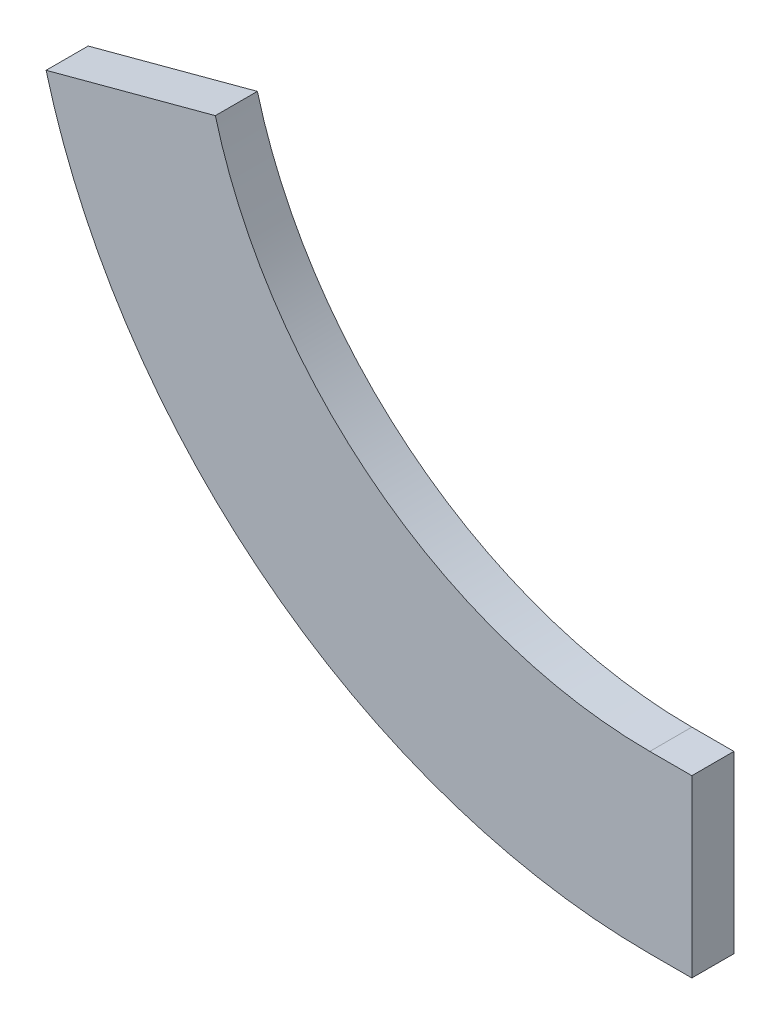
SolidWorks part; units mm, degrees
ref_plane "Front Plane" through (0, 0, 0) normal (0, 0, 1) x (1, 0, 0)
ref_plane "Top Plane" through (0, 0, 0) normal (0, 1, 0) x (1, 0, 0)
ref_plane "Right Plane" through (0, 0, 0) normal (1, 0, 0) x (0, 0, -1)
sketch "Sketch1" plane through (0, 0, 0) normal (0, 0, 1) x (1, 0, 0)
  line L0 (-79.4411, -31.75) -> (-82.4891, -31.75)
  line L1 (-113.979, -7.587) -> (-126.2462, -10.874)
  line L2 (-82.4891, -44.45) -> (-79.4411, -44.45)
  line L3 (-79.4411, -44.45) -> (-79.4411, -31.75)
  line L4 (-79.4411, -44.704) -> (-79.4411, -31.496) construction
  line L5 (-79.4411, -31.496) -> (-82.4891, -31.496) construction
  line L6 (-79.4411, -44.704) -> (-82.4891, -44.704) construction
  line L7 (-82.4891, -59.182) -> (-82.4891, -20.828) construction
  line L8 (-82.4891, -59.182) -> (-82.4891, -20.828) construction
  line L9 (-153.4846, -18.1724) -> (48142.8068, 12922.7798) construction
  arc A0 (-82.4891, -31.75) -> (-113.979, -7.587) centre (-82.4891, 0.8507) cw
  arc A1 (-126.2462, -10.874) -> (-82.4891, -44.45) centre (-82.4891, 0.8507) ccw
  dimension "D1" = 0.254
  dimension "D2" = 0.254
  dimension "D3" = 12.7
  dimension "D4" = 75
extrude "Boss-Extrude1" add sketch "Sketch1" along normal mid plane 3.048 contours A0 L1 A1 L2 L3 L0
